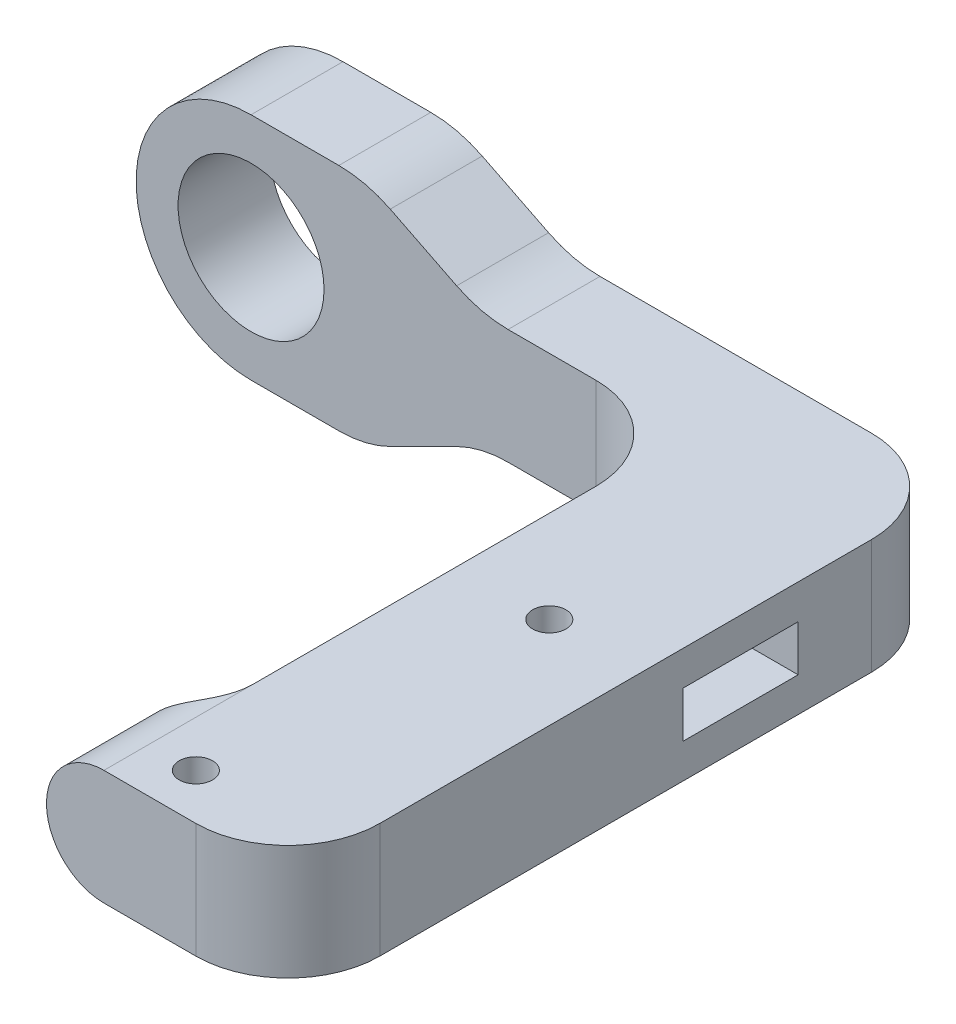
SolidWorks part; units mm, degrees
ref_plane "Face" through (0, 0, 0) normal (0, 0, 1) x (1, 0, 0)
ref_plane "Dessus" through (0, 0, 0) normal (0, 1, 0) x (1, 0, 0)
ref_plane "Droite" through (0, 0, 0) normal (1, 0, 0) x (0, 0, -1)
sketch "Sketch1" plane through (0, 0, 0) normal (0, 0, 1) x (1, 0, 0)
  line L0 (-8, 5) -> (-8, -5)
  line L1 (-8, -5) -> (8, -5)
  line L2 (8, -5) -> (8, 5)
  line L3 (8, 5) -> (-8, 5)
  dimension "D1" = 10
  dimension "D2" = 16
  dimension "D3" = 8
  dimension "D4" = 5
extrude "Boss-Extrude1" add sketch "Sketch1" along normal blind 58.8
ref_plane "Plane1" through (0, 0, 58.8) normal (0, 0, 1) x (1, 0, 0)
sketch "Sketch2" plane through (0, 0, 58.8) normal (0, 0, 1) x (1, 0, 0)
  line L0 (-8, 5) -> (-8, -5)
  arc A0 (-8, 5) -> (-8, -5) centre (-8, 0) ccw
extrude "Boss-Extrude2" add sketch "Sketch2" against normal blind 8
sketch "Sketch4" plane through (0, 0, 0) normal (0, 0, 1) x (1, 0, 0)
  line L0 (-8, 5) -> (-8, -5)
  line L1 (-8, -5) -> (-26, -5)
  line L2 (-26, -5) -> (-36, -10)
  line L3 (-36, -10) -> (-46, -10)
  line L4 (-46, 10) -> (-36, 10)
  line L5 (-36, 10) -> (-26, 5)
  line L6 (-26, 5) -> (-8, 5)
  line L8 (0, 5) -> (0, -5) construction
  line L9 (8, 5) -> (-8, 5) construction
  line L10 (-8, -5) -> (8, -5) construction
  arc A0 (-46, -10) -> (-46, 10) centre (-46, 0) cw
  circle A1 centre (-46, 0) radius 6.35
  dimension "D1" = 10
  dimension "D8" = 12.7
  dimension "D2" = 38
  dimension "D3" = 5
  dimension "D4" = 10
  dimension "D5" = 10
  dimension "D6" = 10
  dimension "D7" = 10
extrude "Boss-Extrude4" add sketch "Sketch4" along normal blind 8
sketch "Sketch7" plane through (0, -5, 0) normal (0, -1, 0) x (1, 0, 0)
  line L0 (-8, 58.8) -> (8, 58.8) construction
  circle A0 centre (-4, 54.8) radius 1.45
  dimension "D1" = 4
  dimension "D3" = 2.9
  dimension "D2" = 4
extrude "Cut-Extrude1" cut sketch "Sketch7" against normal through all
sketch "Sketch13" plane through (0, 5, 0) normal (0, 1, 0) x (1, 0, 0)
  line L0 (8, -58.8) -> (8, 0) construction
  line L1 (8, 0) -> (-26, 0) construction
  circle A0 centre (0, -28.05) radius 1.45
  dimension "D3" = 2.9
  dimension "D1" = 8
  dimension "D2" = 28.05
extrude "Cut-Extrude5" cut sketch "Sketch13" against normal through all
sketch "Sketch14" plane through (-8, 0, 0) normal (-1, 0, 0) x (0, 0, 1)
  line L1 (14.4, 2) -> (24.4, 2)
  line L2 (14.4, 2) -> (14.4, -2)
  line L3 (14.4, -2) -> (24.4, -2)
  line L4 (24.4, 2) -> (24.4, -2)
  dimension "D1" = 14.4
  dimension "D2" = 3
  dimension "D3" = 4
  dimension "D4" = 10
extrude "Cut-Extrude6" cut sketch "Sketch14" against normal through all
fillet "Fillet1" radius 8 2 edges at (8, 0, 58.8) (8, 0, 0)
fillet "Fillet4" radius 10 4 edges at (-36, -10, 4) (-26, -5, 4) (-36, 10, 4) (-26, 5, 4)
fillet "Fillet5" radius 5 1 edges at (-8, 0, 50.8)
fillet "Fillet6" radius 8 1 edges at (-8, 0, 8)
